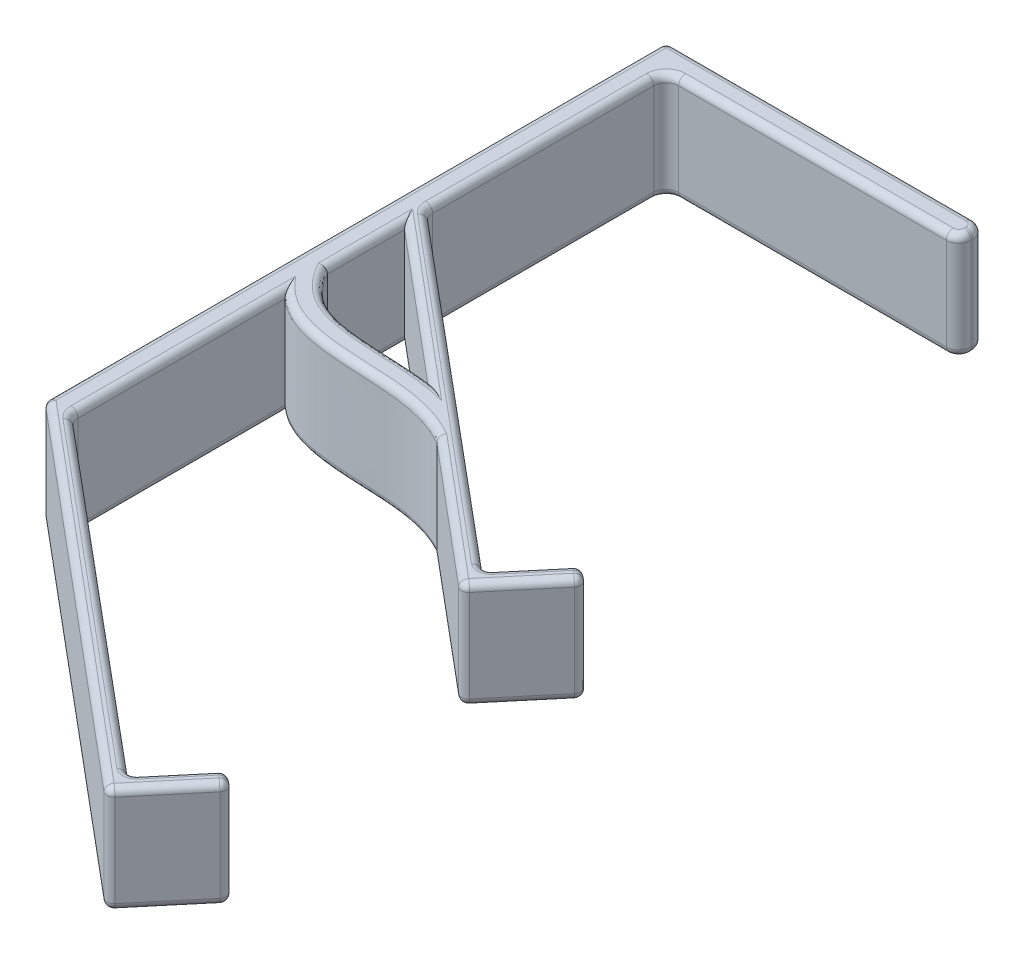
SolidWorks part; units mm, degrees
ref_plane "Front Plane" through (0, 0, 0) normal (0, 0, 1) x (1, 0, 0)
ref_plane "Top Plane" through (0, 0, 0) normal (0, 1, 0) x (1, 0, 0)
ref_plane "Right Plane" through (0, 0, 0) normal (1, 0, 0) x (0, 0, -1)
sketch "Sketch1" plane through (0, 0, 0) normal (0, 1, 0) x (1, 0, 0)
  line L1 (-23.6981, 0) -> (-23.6981, -35)
  line L2 (-23.6981, -35) -> (-3.207, -52.1941)
  line L3 (-2.6435, -52.1448) -> (0.0563, -48.9274)
  line L4 (-21.4981, -1.5) -> (-6.3981, -1.5)
  line L5 (-5.6981, -0.8) -> (-5.6981, -0.7)
  line L6 (-21.9473, -35.2103) -> (-3.3286, -50.7842)
  line L7 (-2.7655, -50.7345) -> (-0.7098, -48.2846)
  line L8 (-6.3981, 0) -> (-23.6981, 0)
  line L9 (-21.9473, -15.2103) -> (-3.3286, -30.7842)
  line L11 (-22.1981, -2.2) -> (-22.1981, -34.6733)
  line L13 (-23.6981, -15) -> (-3.207, -32.1941)
  line L14 (-0.1463, -48.2353) -> (0.007, -48.3639)
  line L15 (-23.6981, -35) -> (-23.6981, -40.9708)
  line L16 (-2.7655, -30.7345) -> (-0.7098, -28.2846)
  line L17 (-2.6435, -32.1448) -> (0.0563, -28.9274)
  line L18 (-0.1463, -28.2353) -> (0.007, -28.3639)
  line L19 (-23.6981, -15) -> (-23.6981, -20.9708)
  arc A0 (-21.9473, -35.2103) -> (-22.1981, -34.6733) centre (-21.4981, -34.6733) cw
  arc A1 (-5.6981, -0.8) -> (-6.3981, -1.5) centre (-6.3981, -0.8) cw
  arc A2 (-5.6981, -0.7) -> (-6.3981, 0) centre (-6.3981, -0.7) ccw
  arc A3 (-21.4981, -1.5) -> (-22.1981, -2.2) centre (-21.4981, -2.2) ccw
  arc A4 (0.007, -48.3639) -> (0.0563, -48.9274) centre (-0.2502, -48.6703) cw
  arc A5 (-0.1463, -48.2353) -> (-0.7098, -48.2846) centre (-0.4034, -48.5418) ccw
  arc A6 (-2.7655, -50.7345) -> (-3.3286, -50.7842) centre (-3.0719, -50.4774) cw
  arc A7 (-2.6435, -52.1448) -> (-3.207, -52.1941) centre (-2.9499, -51.8877) cw
  arc A8 (-2.7655, -30.7345) -> (-3.3286, -30.7842) centre (-3.0719, -30.4774) cw
  arc A9 (-2.6435, -32.1448) -> (-3.207, -32.1941) centre (-2.9499, -31.8877) cw
  arc A10 (-0.1463, -28.2353) -> (-0.7098, -28.2846) centre (-0.4034, -28.5418) ccw
  arc A11 (0.007, -28.3639) -> (0.0563, -28.9274) centre (-0.2502, -28.6703) cw
  arc A12 (-21.9473, -15.2103) -> (-22.1981, -14.6733) centre (-21.4981, -14.6733) cw
  spline S0 degree 3 poles (-23.6981, -35) (-25.326, -38.0364) (-23.6613, -43.2019) (-17.0661, -44.9895) (-13.4856, -44.2741) (-10.8799, -45.7558) knots 0 0 0 0 0.474938 0.582926 1 1 1 1
  spline S1 degree 1 poles (-22.3761, -35.7087) (-10.1385, -44.4518) knots 0 0 1 1 construction
  spline S2 degree 3 poles (-22.3761, -35.7087) (-22.6914, -36.2967) (-23.0309, -37.6113) (-22.7133, -39.7689) (-21.8462, -41.2954) (-20.9238, -42.1462) (-19.9339, -42.6997) (-18.1453, -43.0491) (-16.1327, -43.1062) (-14.3783, -43.2086) (-12.9974, -43.3906) (-11.5801, -43.752) (-10.594, -44.1928) (-10.1385, -44.4518) knots 0 0 0 0 0.125 0.25 0.375 0.4375 0.5 0.625 0.75 0.8125 0.875 0.9375 1 1 1 1 only from (-22.5148, -35.993) to (-13.822, -43.2871)
  spline S3 degree 1 poles (-22.3443, -20.3249) (-10.1385, -24.4518) knots 0 0 1 1 construction
  spline S4 degree 3 poles (-23.6981, -20.9708) (-23.4402, -21.5114) (-22.7349, -22.6043) (-21.1911, -23.8715) (-17.0661, -24.9895) (-13.4856, -24.2741) (-10.8799, -25.7558) knots 0.289345 0.289345 0.289345 0.289345 0.374546 0.474938 0.582926 1 1 1 1
  spline S5 degree 3 poles (-22.3443, -20.3249) (-22.1402, -20.7528) (-21.594, -21.5865) (-20.7626, -22.2664) (-20.0059, -22.6098) (-19.0825, -22.8747) (-17.7626, -23.0479) (-16.0421, -23.1172) (-14.1764, -23.2086) (-12.5132, -23.4805) (-11.1583, -23.9322) (-10.4657, -24.2658) (-10.1385, -24.4518) knots 0.289345 0.289345 0.289345 0.289345 0.378177 0.467009 0.511424 0.55584 0.644672 0.733504 0.822336 0.911168 0.955584 1 1 1 1 only from (-22.1981, -20.6097) to (-13.822, -23.2871)
  point P12 (-22.1981, -35.0004)
  point P17 (-5.6981, -1.5)
  point P29 (-5.6981, 0)
  point P34 (0.3134, -48.621)
  point P39 (-3.0222, -51.0405)
  point P42 (-2.9006, -52.4512)
  dimension "D9" = 0.7
  dimension "D10" = 0.4
  dimension "D1" = 1
  dimension "D2" = 5
  dimension "D3" = 130
  dimension "D4" = 35
  dimension "D6" = 25
  dimension "D8" = 1.5
  dimension "D5" = 18
  dimension "D7" = 1.5
  dimension "D11" = 1.5
  dimension "D13" = 1.5
  dimension "D12" = 2
extrude "Boss-Extrude1" add sketch "Sketch1" along normal blind 6 contours L9 A12 L11 L13 A9 L17 A11 L18 A10 L16 A8 | S5 L11 S4 L13 | S4 L1 L2 A7 L3 A4 L14 A5 L7 A6 L6 A0 L11 | A3 L4 A1 L5 A2 L8 L1 L13 L11 | L1 S4 L11 L13 region at (-15.0481, 0, 0.2426) region at (-22.9341, 0, 18.8933) region at (-23.2564, 0, 22.2119) region at (-17.4915, 0, 19.5481) region at (-17.5478, 0, 23.5982) region at (-12.8095, 0, 23.6276) region at (-12.8093, 0, 43.6272)
fillet "Fillet1" radius 0.4 66 edges at (-22.1981, 0, 18.4342) (-18.0101, 0, 19.7729) (-7.0434, 0, 28.9749) (-2.915, 0, 32.2862) (-1.2936, 0, 30.5361) (0.1483, 0, 28.6354) (-0.0697, 0, 28.2996) (-0.4382, 0, 28.1433) (-1.7376, 0, 29.5096) (-3.0367, 0, 30.8759) (-22.1323, 0, 14.9697) (-22.1981, 0, 8.4367) (-21.9931, 0, 1.705) (-13.9481, 0, 1.5) (-5.9032, 0, 1.295) (-5.6981, 0, 0.75) (-5.9032, 0, 0.205) (-15.0481, 0, 0) (-23.6981, 0, 17.5) (-13.4526, 0, 43.5971) (-2.915, 0, 52.2862) (-1.2936, 0, 50.5361) (0.1483, 0, 48.6354) (-0.0697, 0, 48.2996) (-0.4382, 0, 48.1433) (-1.7376, 0, 49.5096) (-3.0367, 0, 50.8759) (-12.6379, 0, 42.9972) (-22.1323, 0, 34.9697) (-22.1981, 0, 28.8361) (-12.6379, 0, 22.9972) (-22.1981, 6, 18.4342) (-18.0101, 6, 19.7729) (-22.1981, 6, 28.8361) (-22.1323, 6, 34.9697) (-12.6379, 6, 42.9972) (-3.0367, 6, 50.8759) (-1.7376, 6, 49.5096) (-0.4382, 6, 48.1433) (-0.0697, 6, 48.2996) (0.1483, 6, 48.6354) (-1.2936, 6, 50.5361) (-2.915, 6, 52.2862) (-13.4526, 6, 43.5971) (-23.6981, 6, 17.5) (-15.0481, 6, 0) (-5.9032, 6, 0.205) (-5.6981, 6, 0.75) (-5.9032, 6, 1.295) (-13.9481, 6, 1.5) (-21.9931, 6, 1.705) (-22.1981, 6, 8.4367) (-22.1323, 6, 14.9697) (-12.6379, 6, 22.9972) (-3.0367, 6, 30.8759) (-1.7376, 6, 29.5096) (-0.4382, 6, 28.1433) (-0.0697, 6, 28.2996) (0.1483, 6, 28.6354) (-1.2936, 6, 30.5361) (-2.915, 6, 32.2862) (-7.0434, 6, 28.9749)
fillet "Fillet2" radius 0.4 6 edges at (-23.581, 5.8828, 34.9454) (-23.581, 0.1172, 34.9454) (-23.581, 5.8828, 0.1172) (-23.581, 0.1172, 0.1172) (-23.6981, 3, 35) (-23.6981, 3, 0)
